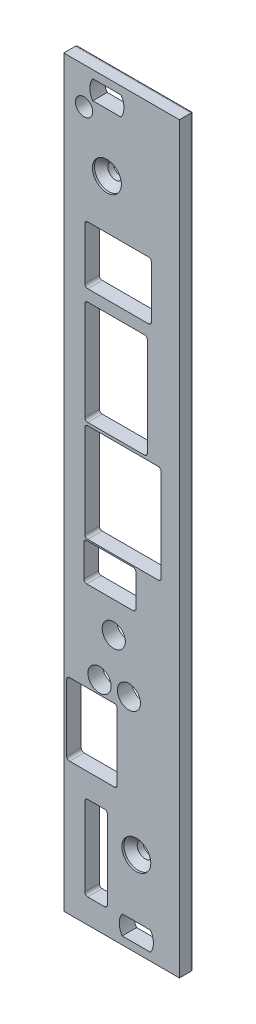
SolidWorks part; units mm, degrees
ref_plane "Front Plane" through (0, 0, 0) normal (0, 0, 1) x (1, 0, 0)
ref_plane "Top Plane" through (0, 0, 0) normal (0, 1, 0) x (1, 0, 0)
ref_plane "Right Plane" through (0, 0, 0) normal (1, 0, 0) x (0, 0, -1)
ref_plane "Plane1" through (0, 0, 2.5) normal (0, 0, 1) x (1, 0, 0)
sketch "Sketch1" plane through (0, 0, 2.5) normal (0, 0, 1) x (1, 0, 0)
  line L0 (12.53, 125.4) -> (-7.45, 125.4)
  line L1 (-7.45, 125.4) -> (-7.45, -3)
  line L2 (-7.45, -3) -> (12.53, -3)
  line L3 (12.53, -3) -> (12.53, 125.4)
extrude "Boss-Extrude1" add sketch "Sketch1" against normal blind 2.5
sketch "Sketch2" plane through (0, 0, 2.5) normal (0, 0, 1) x (1, 0, 0)
  line L0 (2.4454, 124.05) -> (-2.4454, 124.05)
  line L1 (-2.4454, 120.75) -> (2.4454, 120.75)
  arc A0 (-2.4454, 124.05) -> (-2.4454, 120.75) centre (0, 122.4) ccw
  arc A1 (2.4454, 120.75) -> (2.4454, 124.05) centre (0, 122.4) ccw
extrude "Cut-Extrude1" cut sketch "Sketch2" against normal through all
sketch "Sketch3" plane through (0, 0, 2.5) normal (0, 0, 1) x (1, 0, 0)
  line L0 (7.5254, 1.65) -> (2.6346, 1.65)
  line L1 (2.6346, -1.65) -> (7.5254, -1.65)
  arc A0 (2.6346, 1.65) -> (2.6346, -1.65) centre (5.08, 0) ccw
  arc A1 (7.5254, -1.65) -> (7.5254, 1.65) centre (5.08, 0) ccw
extrude "Cut-Extrude2" cut sketch "Sketch3" against normal through all
sketch "Sketch4" plane through (0, 0, 0) normal (0, 0, -1) x (-1, 0, 0)
  line L0 (3.82, 15.8) -> (-0.08, 15.8)
  line L1 (-0.08, 15.8) -> (-0.08, 1.2)
  line L2 (-0.08, 1.2) -> (3.82, 1.2)
  line L3 (3.82, 1.2) -> (3.82, 15.8)
extrude "Cut-Extrude3" cut sketch "Sketch4" against normal through all
hole_wizard "Ø3.0 (3) Diameter Hole1" positions "Sketch6" profile "Sketch5" hole size "Ø3.0" standard "ANSI Metric"
sketch "Sketch6" plane through (0, 0, 2.5) normal (0, 0, 1) x (1, 0, 0)
  point P0 (-3.95, 119.1)
sketch "Sketch5" plane through (-3.95, 119.1, 2.5) normal (1, 0, 0) x (0, -1, 0)
  line L0 (0, 0) -> (0, 2.5)
  line L1 (0, 2.5) -> (1.5, 2.5)
  line L2 (1.5, 2.5) -> (1.5, 0)
  line L5 (1.5, 0) -> (0, 0)
  line L11 (0, -6.35) -> (0, 107.95) construction
  dimension "Thru Hole Dia." = 3
  dimension "Thru Hole Depth" = 2.5
hole_wizard "CSK for M2.5 Flat Head Machine Screw1" positions "Sketch8" profile "Sketch7" countersink size "M2.5" standard "ANSI Metric"
sketch "Sketch8" plane through (0, 0, 2.5) normal (0, 0, 1) x (1, 0, 0)
  point P0 (5.08, 11.7)
  point P1 (0, 110.7)
sketch "Sketch7" plane through (5.08, 11.7, 2.5) normal (1, 0, 0) x (0, -1, 0)
  line L0 (0, 0) -> (0, 2.5)
  line L1 (0, 2.5) -> (1.35, 2.5)
  line L2 (1.35, 2.5) -> (1.35, 1.5)
  line L3 (1.35, 1.5) -> (2.5, 0.35)
  line L4 (2.5, 0.35) -> (2.5, 0)
  line L6 (2.5, 0) -> (0, 0)
  line L7 (-1.35, 1.5) -> (-2.5, 0.35) construction
  line L11 (0, -6.35) -> (0, 107.95) construction
  dimension "Thru Hole Dia." = 2.7
  dimension "Thru Hole Depth" = 2.5
  dimension "C'Sink Dia." = 5
  dimension "C'Sink Angle" = 90
  dimension "Head Clearance" = 0.35
ref_plane "Board bottom" through (0, 11.2, 0) normal (0, -1, 0) x (-1, 0, 0)
ref_plane "Board top" through (0, 111.2, 0) normal (0, 1, 0) x (1, 0, 0)
ref_plane "Board upper surface" through (-3.82, 0, 0) normal (1, 0, 0) x (0, 0, -1)
ref_plane "Board lower surface" through (-5.42, 0, 0) normal (1, 0, 0) x (0, 0, -1)
sketch "Sketch9" plane through (0, 0, 2.5) normal (0, 0, 1) x (1, 0, 0)
  line L0 (-3.82, 19.95) -> (-3.82, 32.45) construction
  line L1 (-3.82, 19.95) -> (1.78, 19.95)
  line L2 (-3.82, 32.45) -> (1.78, 32.45)
  line L3 (1.78, 19.95) -> (1.78, 32.45)
  line L4 (-3.82, -47.3899) -> (-3.82, 47.3899) construction
  line L5 (-28.8918, 11.2) -> (28.8918, 11.2) construction
  line L6 (-3.82, 32.45) -> (-3.82, 19.95) construction
  line L7 (-3.82, 32.45) -> (-6.95, 32.45)
  line L8 (-3.82, 19.95) -> (-6.95, 19.95)
  line L9 (-6.95, 32.45) -> (-6.95, 19.95)
  line L10 (-6.95, 32.45) -> (1.78, 19.95) construction
  line L11 (1.78, 32.45) -> (-6.95, 19.95) construction
  line L12 (-7.45, 125.4) -> (-7.45, -3) construction
  point P8 (-2.585, 26.2)
  dimension "D1" = 8.75
  dimension "D2" = 21.25
  dimension "D3" = 5.6
  dimension "D4" = 3.13
  dimension "D5" = 15
  dimension "D6" = 1.235
  dimension "D7" = 12.5
  dimension "D8" = 8.73
  dimension "D9" = 0.5
extrude "USB" cut sketch "Sketch9" against normal through all
sketch "Sketch10" plane through (0, 0, 2.5) normal (0, 0, 1) x (1, 0, 0)
  line L0 (-3.82, 34.72) -> (3.8, 34.72) construction
  line L1 (-3.82, -21.0154) -> (-3.82, 21.0154) construction
  line L3 (-6.1147, 11.2) -> (6.1147, 11.2) construction
  circle A0 centre (-1.28, 34.72) radius 2
  circle A1 centre (3.8, 34.72) radius 2
  dimension "D1" = 4
  dimension "D2" = 4
  dimension "D3" = 2.54
  dimension "D4" = 5.08
  dimension "D5" = 23.52
extrude "LEDs" cut sketch "Sketch10" against normal through all
sketch "Sketch11" plane through (0, 0, 2.5) normal (0, 0, 1) x (1, 0, 0)
  line L0 (1.18, 42.62) -> (-3.82, 42.62) construction
  line L1 (-3.82, -21.0154) -> (-3.82, 21.0154) construction
  line L3 (-6.1147, 11.2) -> (6.1147, 11.2) construction
  circle A0 centre (1.18, 42.62) radius 2
  dimension "D1" = 4
  dimension "D2" = 5
  dimension "D3" = 31.42
extrude "Single LED" cut sketch "Sketch11" against normal through all
sketch "Sketch13" plane through (0, 0, 2.5) normal (0, 0, 1) x (1, 0, 0)
  line L0 (0.505, 51.2) -> (-3.82, 51.2) construction
  line L1 (-3.82, -21.0154) -> (-3.82, 21.0154) construction
  line L4 (-3.995, 47.95) -> (5.005, 47.95)
  line L5 (-3.995, 47.95) -> (-3.995, 54.45)
  line L6 (-3.995, 54.45) -> (5.005, 54.45)
  line L7 (5.005, 47.95) -> (5.005, 54.45)
  line L8 (-3.995, 47.95) -> (5.005, 54.45) construction
  line L9 (-3.995, 54.45) -> (5.005, 47.95) construction
  line L10 (-6.1147, 11.2) -> (6.1147, 11.2) construction
  point P1 (0.505, 51.2)
  point P2 (0, 0)
  point P6 (0, 0)
  dimension "D1" = 6.5
  dimension "D2" = 40
  dimension "D3" = 4.325
  dimension "D4" = 9
extrude "Disable comms" cut sketch "Sketch13" against normal through all
sketch "Sketch14" plane through (0, 0, 2.5) normal (0, 0, 1) x (1, 0, 0)
  line L0 (-3.82, 54.7) -> (-3.82, 71.7)
  line L1 (-3.82, 54.7) -> (9.38, 54.7)
  line L2 (-3.82, 71.7) -> (9.38, 71.7)
  line L3 (9.38, 54.7) -> (9.38, 71.7)
  line L4 (-3.82, -21.0154) -> (-3.82, 21.0154) construction
  line L5 (-6.1147, 11.2) -> (6.1147, 11.2) construction
  dimension "D1" = 43.5
  dimension "D2" = 60.5
  dimension "D3" = 13.2
extrude "RJ45" cut sketch "Sketch14" against normal through all
sketch "Sketch15" plane through (0, 0, 2.5) normal (0, 0, 1) x (1, 0, 0)
  line L0 (-3.82, 72.2) -> (-3.82, 90.2)
  line L1 (-3.82, 72.2) -> (6.98, 72.2)
  line L2 (-3.82, 90.2) -> (6.98, 90.2)
  line L3 (6.98, 72.2) -> (6.98, 90.2)
  line L4 (-3.82, -21.0154) -> (-3.82, 21.0154) construction
  line L5 (-6.1147, 11.2) -> (6.1147, 11.2) construction
  dimension "D1" = 61
  dimension "D2" = 79
  dimension "D3" = 10.8
extrude "Output" cut sketch "Sketch15" against normal through all
sketch "Sketch16" plane through (0, 0, 2.5) normal (0, 0, 1) x (1, 0, 0)
  line L0 (-3.82, 92.2) -> (-3.82, 102.2)
  line L1 (-3.82, 92.2) -> (7.68, 92.2)
  line L2 (-3.82, 102.2) -> (7.68, 102.2)
  line L3 (7.68, 92.2) -> (7.68, 102.2)
  line L4 (-3.82, -21.0154) -> (-3.82, 21.0154) construction
  line L5 (-6.1147, 11.2) -> (6.1147, 11.2) construction
  dimension "D1" = 81
  dimension "D2" = 91
  dimension "D3" = 11.5
extrude "Power" cut sketch "Sketch16" against normal through all
fillet "Fillets" radius 0.5 24 edges at (1.78, 19.95, 1.25) (-6.95, 19.95, 1.25) (-6.95, 32.45, 1.25) (1.78, 32.45, 1.25) (0.08, 1.2, 1.25) (-3.82, 1.2, 1.25) (-3.82, 15.8, 1.25) (0.08, 15.8, 1.25) (9.38, 71.7, 1.25) (6.98, 90.2, 1.25) (7.68, 102.2, 1.25) (-3.82, 71.7, 1.25) (-3.82, 90.2, 1.25) (-3.82, 102.2, 1.25) (-3.82, 54.7, 1.25) (-3.82, 72.2, 1.25) (-3.82, 92.2, 1.25) (9.38, 54.7, 1.25) (6.98, 72.2, 1.25) (7.68, 92.2, 1.25) (-3.995, 47.95, 1.25) (5.005, 47.95, 1.25) (5.005, 54.45, 1.25) (-3.995, 54.45, 1.25)
fillet "Fillet2" radius 0.5 4 edges at (12.53, 61.2, 0) (2.54, -3, 0) (-7.45, 61.2, 0) (2.54, 125.4, 0) type face fillet first side face at (2.54, -3, 1.25) first side face at (-7.45, 61.2, 1.25) first side face at (12.53, 61.2, 1.25) first side face at (2.54, 125.4, 1.25) second side face at (1.93, 97.2, 0)
ref_plane "Plane2" through (-3.495, 54.45, 2.5) normal (-1, 0, 0) x (0, 0, 1)
equation "\"D6@Sketch9\"=2.47/2"
